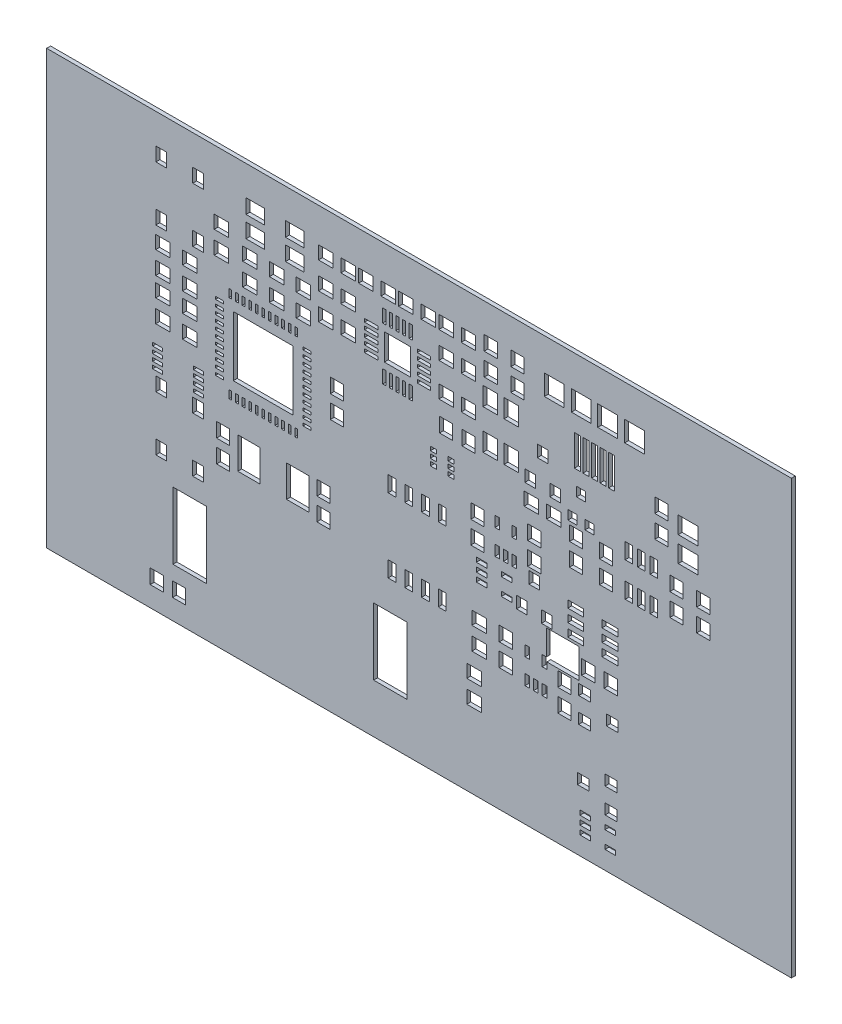
SolidWorks part; units mm, degrees
ref_plane "Front Plane" through (0, 0, 0) normal (0, 0, 1) x (1, 0, 0)
ref_plane "Top Plane" through (0, 0, 0) normal (0, 1, 0) x (1, 0, 0)
ref_plane "Right Plane" through (0, 0, 0) normal (1, 0, 0) x (0, 0, -1)
sketch "Model" plane through (0, 0, 0) normal (0, 0, 1) x (1, 0, 0)
  line L0 (20.5761, 267.496) -> (23.1161, 267.496)
  line L1 (23.1161, 267.496) -> (23.1161, 272.576)
  line L2 (23.1161, 272.576) -> (20.5761, 272.576)
  line L3 (20.5761, 272.576) -> (20.5761, 267.496)
  line L4 (5.3361, 267.496) -> (7.8761, 267.496)
  line L5 (7.8761, 267.496) -> (7.8761, 272.576)
  line L6 (7.8761, 272.576) -> (5.3361, 272.576)
  line L7 (5.3361, 272.576) -> (5.3361, 267.496)
  line L8 (34.554, 274.019) -> (35.554, 274.019)
  line L9 (35.554, 274.019) -> (35.554, 275.119)
  line L10 (35.554, 275.119) -> (34.554, 275.119)
  line L11 (34.554, 275.119) -> (34.554, 274.019)
  line L12 (34.554, 272.319) -> (35.554, 272.319)
  line L13 (35.554, 272.319) -> (35.554, 273.4189)
  line L14 (35.554, 273.4189) -> (34.554, 273.4189)
  line L15 (34.554, 273.4189) -> (34.554, 272.319)
  line L16 (43.7019, 286.724) -> (45.2019, 286.724)
  line L17 (45.2019, 286.724) -> (45.2019, 288.0239)
  line L18 (45.2019, 288.0239) -> (43.7019, 288.0239)
  line L19 (43.7019, 288.0239) -> (43.7019, 286.724)
  line L20 (43.7019, 288.624) -> (45.2019, 288.624)
  line L21 (45.2019, 288.624) -> (45.2019, 289.924)
  line L22 (45.2019, 289.924) -> (43.7019, 289.924)
  line L23 (43.7019, 289.924) -> (43.7019, 288.624)
  line L24 (24.1781, 293.0311) -> (25.2781, 293.0311)
  line L25 (25.2781, 293.0311) -> (25.2781, 294.031)
  line L26 (25.2781, 294.031) -> (24.1781, 294.031)
  line L27 (24.1781, 294.031) -> (24.1781, 293.0311)
  line L28 (22.4781, 293.0311) -> (23.5782, 293.0311)
  line L29 (23.5782, 293.0311) -> (23.5782, 294.031)
  line L30 (23.5782, 294.031) -> (22.4781, 294.031)
  line L31 (22.4781, 294.031) -> (22.4781, 293.0311)
  line L32 (41.92, 287.4319) -> (42.92, 287.4319)
  line L33 (42.92, 287.4319) -> (42.92, 288.532)
  line L34 (42.92, 288.532) -> (41.92, 288.532)
  line L35 (41.92, 288.532) -> (41.92, 287.4319)
  line L36 (41.92, 289.132) -> (42.92, 289.132)
  line L37 (42.92, 289.132) -> (42.92, 290.232)
  line L38 (42.92, 290.232) -> (41.92, 290.232)
  line L39 (41.92, 290.232) -> (41.92, 289.132)
  line L40 (30.109, 274.781) -> (31.109, 274.781)
  line L41 (31.109, 274.781) -> (31.109, 275.8809)
  line L42 (31.109, 275.8809) -> (30.109, 275.8809)
  line L43 (30.109, 275.8809) -> (30.109, 274.781)
  line L44 (30.109, 273.0811) -> (31.109, 273.0811)
  line L45 (31.109, 273.0811) -> (31.109, 274.181)
  line L46 (31.109, 274.181) -> (30.109, 274.181)
  line L47 (30.109, 274.181) -> (30.109, 273.0811)
  line L48 (17.282, 282.9869) -> (18.2821, 282.9869)
  line L49 (18.2821, 282.9869) -> (18.2821, 284.087)
  line L50 (18.2821, 284.087) -> (17.282, 284.087)
  line L51 (17.282, 284.087) -> (17.282, 282.9869)
  line L52 (17.282, 284.687) -> (18.2821, 284.687)
  line L53 (18.2821, 284.687) -> (18.2821, 285.787)
  line L54 (18.2821, 285.787) -> (17.282, 285.787)
  line L55 (17.282, 285.787) -> (17.282, 284.687)
  line L56 (16.2661, 275.748) -> (17.266, 275.748)
  line L57 (17.266, 275.748) -> (17.266, 276.8481)
  line L58 (17.266, 276.8481) -> (16.2661, 276.8481)
  line L59 (16.2661, 276.8481) -> (16.2661, 275.748)
  line L60 (16.2661, 277.4481) -> (17.266, 277.4481)
  line L61 (17.266, 277.4481) -> (17.266, 278.548)
  line L62 (17.266, 278.548) -> (16.2661, 278.548)
  line L63 (16.2661, 278.548) -> (16.2661, 277.4481)
  line L64 (43.063, 282.86) -> (44.063, 282.86)
  line L65 (44.063, 282.86) -> (44.063, 283.96)
  line L66 (44.063, 283.96) -> (43.063, 283.96)
  line L67 (43.063, 283.96) -> (43.063, 282.86)
  line L68 (43.063, 284.56) -> (44.063, 284.56)
  line L69 (44.063, 284.56) -> (44.063, 285.6601)
  line L70 (44.063, 285.6601) -> (43.063, 285.6601)
  line L71 (43.063, 285.6601) -> (43.063, 284.56)
  line L72 (45.095, 282.86) -> (46.095, 282.86)
  line L73 (46.095, 282.86) -> (46.095, 283.96)
  line L74 (46.095, 283.96) -> (45.095, 283.96)
  line L75 (45.095, 283.96) -> (45.095, 282.86)
  line L76 (45.095, 284.56) -> (46.095, 284.56)
  line L77 (46.095, 284.56) -> (46.095, 285.6601)
  line L78 (46.095, 285.6601) -> (45.095, 285.6601)
  line L79 (45.095, 285.6601) -> (45.095, 284.56)
  line L80 (8.6461, 277.4481) -> (9.646, 277.4481)
  line L81 (9.646, 277.4481) -> (9.646, 278.548)
  line L82 (9.646, 278.548) -> (8.6461, 278.548)
  line L83 (8.6461, 278.548) -> (8.6461, 277.4481)
  line L84 (8.6461, 275.748) -> (9.646, 275.748)
  line L85 (9.646, 275.748) -> (9.646, 276.8481)
  line L86 (9.646, 276.8481) -> (8.6461, 276.8481)
  line L87 (8.6461, 276.8481) -> (8.6461, 275.748)
  line L88 (18.0821, 290.999) -> (19.1821, 290.999)
  line L89 (19.1821, 290.999) -> (19.1821, 291.999)
  line L90 (19.1821, 291.999) -> (18.0821, 291.999)
  line L91 (18.0821, 291.999) -> (18.0821, 290.999)
  line L92 (16.382, 290.999) -> (17.4821, 290.999)
  line L93 (17.4821, 290.999) -> (17.4821, 291.999)
  line L94 (17.4821, 291.999) -> (16.382, 291.999)
  line L95 (16.382, 291.999) -> (16.382, 290.999)
  line L96 (37.729, 282.352) -> (38.729, 282.352)
  line L97 (38.729, 282.352) -> (38.729, 283.452)
  line L98 (38.729, 283.452) -> (37.729, 283.452)
  line L99 (37.729, 283.452) -> (37.729, 282.352)
  line L100 (37.729, 284.052) -> (38.729, 284.052)
  line L101 (38.729, 284.052) -> (38.729, 285.152)
  line L102 (38.729, 285.152) -> (37.729, 285.152)
  line L103 (37.729, 285.152) -> (37.729, 284.052)
  line L104 (28.966, 293.3231) -> (29.9659, 293.3231)
  line L105 (29.9659, 293.3231) -> (29.9659, 294.423)
  line L106 (29.9659, 294.423) -> (28.966, 294.423)
  line L107 (28.966, 294.423) -> (28.966, 293.3231)
  line L108 (28.966, 291.623) -> (29.9659, 291.623)
  line L109 (29.9659, 291.623) -> (29.9659, 292.7231)
  line L110 (29.9659, 292.7231) -> (28.966, 292.7231)
  line L111 (28.966, 292.7231) -> (28.966, 291.623)
  line L112 (30.998, 293.3231) -> (31.998, 293.3231)
  line L113 (31.998, 293.3231) -> (31.998, 294.423)
  line L114 (31.998, 294.423) -> (30.998, 294.423)
  line L115 (30.998, 294.423) -> (30.998, 293.3231)
  line L116 (30.998, 291.623) -> (31.998, 291.623)
  line L117 (31.998, 291.623) -> (31.998, 292.7231)
  line L118 (31.998, 292.7231) -> (30.998, 292.7231)
  line L119 (30.998, 292.7231) -> (30.998, 291.623)
  line L120 (25.5261, 293.0311) -> (26.6261, 293.0311)
  line L121 (26.6261, 293.0311) -> (26.6261, 294.031)
  line L122 (26.6261, 294.031) -> (25.5261, 294.031)
  line L123 (25.5261, 294.031) -> (25.5261, 293.0311)
  line L124 (27.2261, 293.0311) -> (28.3261, 293.0311)
  line L125 (28.3261, 293.0311) -> (28.3261, 294.031)
  line L126 (28.3261, 294.031) -> (27.2261, 294.031)
  line L127 (27.2261, 294.031) -> (27.2261, 293.0311)
  line L128 (25.5261, 290.999) -> (26.6261, 290.999)
  line L129 (26.6261, 290.999) -> (26.6261, 291.999)
  line L130 (26.6261, 291.999) -> (25.5261, 291.999)
  line L131 (25.5261, 291.999) -> (25.5261, 290.999)
  line L132 (27.2261, 290.999) -> (28.3261, 290.999)
  line L133 (28.3261, 290.999) -> (28.3261, 291.999)
  line L134 (28.3261, 291.999) -> (27.2261, 291.999)
  line L135 (27.2261, 291.999) -> (27.2261, 290.999)
  line L136 (33.6826, 277.5036) -> (33.6826, 275.577)
  line L137 (33.3701, 275.577) -> (33.6826, 275.577)
  line L138 (36.1719, 275.2684) -> (33.7201, 275.2684)
  line L139 (33.7201, 275.2684) -> (33.7201, 274.777)
  line L140 (9.5937, 280.5076) -> (9.7944, 280.5076)
  line L141 (9.7944, 280.5076) -> (9.7944, 281.1084)
  line L142 (9.7944, 281.1084) -> (9.5937, 281.1084)
  line L143 (9.5937, 281.1084) -> (9.5937, 280.5076)
  line L148 (10.0936, 280.5076) -> (10.2945, 280.5076)
  line L149 (10.2945, 280.5076) -> (10.2945, 281.1084)
  line L150 (10.2945, 281.1084) -> (10.0936, 281.1084)
  line L151 (10.0936, 281.1084) -> (10.0936, 280.5076)
  line L156 (10.5937, 280.5076) -> (10.7945, 280.5076)
  line L157 (10.7945, 280.5076) -> (10.7945, 281.1084)
  line L158 (10.7945, 281.1084) -> (10.5937, 281.1084)
  line L159 (10.5937, 281.1084) -> (10.5937, 280.5076)
  line L164 (11.0937, 280.5076) -> (11.2945, 280.5076)
  line L165 (11.2945, 280.5076) -> (11.2945, 281.1084)
  line L166 (11.2945, 281.1084) -> (11.0937, 281.1084)
  line L167 (11.0937, 281.1084) -> (11.0937, 280.5076)
  line L172 (11.5936, 280.5076) -> (11.7946, 280.5076)
  line L173 (11.7946, 280.5076) -> (11.7946, 281.1084)
  line L174 (11.7946, 281.1084) -> (11.5936, 281.1084)
  line L175 (11.5936, 281.1084) -> (11.5936, 280.5076)
  line L180 (12.0937, 280.5076) -> (12.2945, 280.5076)
  line L181 (12.2945, 280.5076) -> (12.2945, 281.1084)
  line L182 (12.2945, 281.1084) -> (12.0937, 281.1084)
  line L183 (12.0937, 281.1084) -> (12.0937, 280.5076)
  line L188 (12.5937, 280.5076) -> (12.7944, 280.5076)
  line L189 (12.7944, 280.5076) -> (12.7944, 281.1084)
  line L190 (12.7944, 281.1084) -> (12.5937, 281.1084)
  line L191 (12.5937, 281.1084) -> (12.5937, 280.5076)
  line L196 (13.0938, 280.5076) -> (13.2945, 280.5076)
  line L197 (13.2945, 280.5076) -> (13.2945, 281.1084)
  line L198 (13.2945, 281.1084) -> (13.0938, 281.1084)
  line L199 (13.0938, 281.1084) -> (13.0938, 280.5076)
  line L204 (13.5937, 280.5076) -> (13.7945, 280.5076)
  line L205 (13.7945, 280.5076) -> (13.7945, 281.1084)
  line L206 (13.7945, 281.1084) -> (13.5937, 281.1084)
  line L207 (13.5937, 281.1084) -> (13.5937, 280.5076)
  line L212 (14.0937, 280.5076) -> (14.2944, 280.5076)
  line L213 (14.2944, 280.5076) -> (14.2944, 281.1084)
  line L214 (14.2944, 281.1084) -> (14.0937, 281.1084)
  line L215 (14.0937, 281.1084) -> (14.0937, 280.5076)
  line L220 (14.5938, 280.5076) -> (14.7945, 280.5076)
  line L221 (14.7945, 280.5076) -> (14.7945, 281.1084)
  line L222 (14.7945, 281.1084) -> (14.5938, 281.1084)
  line L223 (14.5938, 281.1084) -> (14.5938, 280.5076)
  line L228 (15.2187, 281.5326) -> (15.8195, 281.5326)
  line L229 (15.8195, 281.5326) -> (15.8195, 281.7333)
  line L230 (15.8195, 281.7333) -> (15.2187, 281.7333)
  line L231 (15.2187, 281.7333) -> (15.2187, 281.5326)
  line L236 (15.2187, 282.0327) -> (15.8195, 282.0327)
  line L237 (15.8195, 282.0327) -> (15.8195, 282.2334)
  line L238 (15.8195, 282.2334) -> (15.2187, 282.2334)
  line L239 (15.2187, 282.2334) -> (15.2187, 282.0327)
  line L244 (15.2187, 282.5326) -> (15.8195, 282.5326)
  line L245 (15.8195, 282.5326) -> (15.8195, 282.7334)
  line L246 (15.8195, 282.7334) -> (15.2187, 282.7334)
  line L247 (15.2187, 282.7334) -> (15.2187, 282.5326)
  line L252 (15.2187, 283.0326) -> (15.8195, 283.0326)
  line L253 (15.8195, 283.0326) -> (15.8195, 283.2333)
  line L254 (15.8195, 283.2333) -> (15.2187, 283.2333)
  line L255 (15.2187, 283.2333) -> (15.2187, 283.0326)
  line L260 (15.2187, 283.5327) -> (15.8195, 283.5327)
  line L261 (15.8195, 283.5327) -> (15.8195, 283.7334)
  line L262 (15.8195, 283.7334) -> (15.2187, 283.7334)
  line L263 (15.2187, 283.7334) -> (15.2187, 283.5327)
  line L268 (15.2187, 284.0326) -> (15.8195, 284.0326)
  line L269 (15.8195, 284.0326) -> (15.8195, 284.2334)
  line L270 (15.8195, 284.2334) -> (15.2187, 284.2334)
  line L271 (15.2187, 284.2334) -> (15.2187, 284.0326)
  line L276 (15.2187, 284.5325) -> (15.8195, 284.5325)
  line L277 (15.8195, 284.5325) -> (15.8195, 284.7335)
  line L278 (15.8195, 284.7335) -> (15.2187, 284.7335)
  line L279 (15.2187, 284.7335) -> (15.2187, 284.5325)
  line L284 (15.2187, 285.0326) -> (15.8195, 285.0326)
  line L285 (15.8195, 285.0326) -> (15.8195, 285.2334)
  line L286 (15.8195, 285.2334) -> (15.2187, 285.2334)
  line L287 (15.2187, 285.2334) -> (15.2187, 285.0326)
  line L292 (15.2187, 285.5326) -> (15.8195, 285.5326)
  line L293 (15.8195, 285.5326) -> (15.8195, 285.7334)
  line L294 (15.8195, 285.7334) -> (15.2187, 285.7334)
  line L295 (15.2187, 285.7334) -> (15.2187, 285.5326)
  line L300 (15.2187, 286.0326) -> (15.8195, 286.0326)
  line L301 (15.8195, 286.0326) -> (15.8195, 286.2335)
  line L302 (15.8195, 286.2335) -> (15.2187, 286.2335)
  line L303 (15.2187, 286.2335) -> (15.2187, 286.0326)
  line L308 (15.2187, 286.5326) -> (15.8195, 286.5326)
  line L309 (15.8195, 286.5326) -> (15.8195, 286.7334)
  line L310 (15.8195, 286.7334) -> (15.2187, 286.7334)
  line L311 (15.2187, 286.7334) -> (15.2187, 286.5326)
  line L316 (14.5938, 287.1576) -> (14.7945, 287.1576)
  line L317 (14.7945, 287.1576) -> (14.7945, 287.7584)
  line L318 (14.7945, 287.7584) -> (14.5938, 287.7584)
  line L319 (14.5938, 287.7584) -> (14.5938, 287.1576)
  line L324 (14.0937, 287.1576) -> (14.2944, 287.1576)
  line L325 (14.2944, 287.1576) -> (14.2944, 287.7584)
  line L326 (14.2944, 287.7584) -> (14.0937, 287.7584)
  line L327 (14.0937, 287.7584) -> (14.0937, 287.1576)
  line L332 (13.5937, 287.1576) -> (13.7945, 287.1576)
  line L333 (13.7945, 287.1576) -> (13.7945, 287.7584)
  line L334 (13.7945, 287.7584) -> (13.5937, 287.7584)
  line L335 (13.5937, 287.7584) -> (13.5937, 287.1576)
  line L340 (13.0938, 287.1576) -> (13.2945, 287.1576)
  line L341 (13.2945, 287.1576) -> (13.2945, 287.7584)
  line L342 (13.2945, 287.7584) -> (13.0938, 287.7584)
  line L343 (13.0938, 287.7584) -> (13.0938, 287.1576)
  line L348 (12.5937, 287.1576) -> (12.7944, 287.1576)
  line L349 (12.7944, 287.1576) -> (12.7944, 287.7584)
  line L350 (12.7944, 287.7584) -> (12.5937, 287.7584)
  line L351 (12.5937, 287.7584) -> (12.5937, 287.1576)
  line L356 (12.0937, 287.1576) -> (12.2945, 287.1576)
  line L357 (12.2945, 287.1576) -> (12.2945, 287.7584)
  line L358 (12.2945, 287.7584) -> (12.0937, 287.7584)
  line L359 (12.0937, 287.7584) -> (12.0937, 287.1576)
  line L364 (11.5936, 287.1576) -> (11.7946, 287.1576)
  line L365 (11.7946, 287.1576) -> (11.7946, 287.7584)
  line L366 (11.7946, 287.7584) -> (11.5936, 287.7584)
  line L367 (11.5936, 287.7584) -> (11.5936, 287.1576)
  line L372 (11.0937, 287.1576) -> (11.2945, 287.1576)
  line L373 (11.2945, 287.1576) -> (11.2945, 287.7584)
  line L374 (11.2945, 287.7584) -> (11.0937, 287.7584)
  line L375 (11.0937, 287.7584) -> (11.0937, 287.1576)
  line L380 (10.5937, 287.1576) -> (10.7945, 287.1576)
  line L381 (10.7945, 287.1576) -> (10.7945, 287.7584)
  line L382 (10.7945, 287.7584) -> (10.5937, 287.7584)
  line L383 (10.5937, 287.7584) -> (10.5937, 287.1576)
  line L388 (10.0936, 287.1576) -> (10.2945, 287.1576)
  line L389 (10.2945, 287.1576) -> (10.2945, 287.7584)
  line L390 (10.2945, 287.7584) -> (10.0936, 287.7584)
  line L391 (10.0936, 287.7584) -> (10.0936, 287.1576)
  line L396 (9.5937, 287.1576) -> (9.7944, 287.1576)
  line L397 (9.7944, 287.1576) -> (9.7944, 287.7584)
  line L398 (9.7944, 287.7584) -> (9.5937, 287.7584)
  line L399 (9.5937, 287.7584) -> (9.5937, 287.1576)
  line L404 (8.5687, 286.5326) -> (9.1695, 286.5326)
  line L405 (9.1695, 286.5326) -> (9.1695, 286.7334)
  line L406 (9.1695, 286.7334) -> (8.5687, 286.7334)
  line L407 (8.5687, 286.7334) -> (8.5687, 286.5326)
  line L412 (8.5687, 286.0326) -> (9.1695, 286.0326)
  line L413 (9.1695, 286.0326) -> (9.1695, 286.2335)
  line L414 (9.1695, 286.2335) -> (8.5687, 286.2335)
  line L415 (8.5687, 286.2335) -> (8.5687, 286.0326)
  line L420 (8.5687, 285.5326) -> (9.1695, 285.5326)
  line L421 (9.1695, 285.5326) -> (9.1695, 285.7334)
  line L422 (9.1695, 285.7334) -> (8.5687, 285.7334)
  line L423 (8.5687, 285.7334) -> (8.5687, 285.5326)
  line L428 (8.5687, 285.0326) -> (9.1695, 285.0326)
  line L429 (9.1695, 285.0326) -> (9.1695, 285.2334)
  line L430 (9.1695, 285.2334) -> (8.5687, 285.2334)
  line L431 (8.5687, 285.2334) -> (8.5687, 285.0326)
  line L436 (8.5687, 284.5325) -> (9.1695, 284.5325)
  line L437 (9.1695, 284.5325) -> (9.1695, 284.7335)
  line L438 (9.1695, 284.7335) -> (8.5687, 284.7335)
  line L439 (8.5687, 284.7335) -> (8.5687, 284.5325)
  line L444 (8.5687, 284.0326) -> (9.1695, 284.0326)
  line L445 (9.1695, 284.0326) -> (9.1695, 284.2334)
  line L446 (9.1695, 284.2334) -> (8.5687, 284.2334)
  line L447 (8.5687, 284.2334) -> (8.5687, 284.0326)
  line L452 (8.5687, 283.5327) -> (9.1695, 283.5327)
  line L453 (9.1695, 283.5327) -> (9.1695, 283.7334)
  line L454 (9.1695, 283.7334) -> (8.5687, 283.7334)
  line L455 (8.5687, 283.7334) -> (8.5687, 283.5327)
  line L460 (8.5687, 283.0326) -> (9.1695, 283.0326)
  line L461 (9.1695, 283.0326) -> (9.1695, 283.2333)
  line L462 (9.1695, 283.2333) -> (8.5687, 283.2333)
  line L463 (8.5687, 283.2333) -> (8.5687, 283.0326)
  line L468 (8.5687, 282.5326) -> (9.1695, 282.5326)
  line L469 (9.1695, 282.5326) -> (9.1695, 282.7334)
  line L470 (9.1695, 282.7334) -> (8.5687, 282.7334)
  line L471 (8.5687, 282.7334) -> (8.5687, 282.5326)
  line L476 (8.5687, 282.0327) -> (9.1695, 282.0327)
  line L477 (9.1695, 282.0327) -> (9.1695, 282.2334)
  line L478 (9.1695, 282.2334) -> (8.5687, 282.2334)
  line L479 (8.5687, 282.2334) -> (8.5687, 282.0327)
  line L484 (8.5687, 281.5326) -> (9.1695, 281.5326)
  line L485 (9.1695, 281.5326) -> (9.1695, 281.7333)
  line L486 (9.1695, 281.7333) -> (8.5687, 281.7333)
  line L487 (8.5687, 281.7333) -> (8.5687, 281.5326)
  line L492 (9.9188, 281.8576) -> (14.4694, 281.8576)
  line L493 (14.4694, 281.8576) -> (14.4694, 286.4083)
  line L494 (14.4694, 286.4083) -> (9.9188, 286.4083)
  line L495 (9.9188, 286.4083) -> (9.9188, 281.8576)
  line L497 (36.1719, 275.2684) -> (36.1719, 277.5036)
  line L498 (36.1719, 277.5036) -> (33.6826, 277.5036)
  line L500 (38.4152, 289.054) -> (38.8652, 289.054)
  line L501 (38.8652, 289.054) -> (38.8652, 291.404)
  line L502 (38.8652, 291.404) -> (38.4152, 291.404)
  line L503 (38.4152, 291.404) -> (38.4152, 289.054)
  line L504 (37.765, 289.054) -> (38.2151, 289.054)
  line L505 (38.2151, 289.054) -> (38.2151, 291.404)
  line L506 (38.2151, 291.404) -> (37.765, 291.404)
  line L507 (37.765, 291.404) -> (37.765, 289.054)
  line L508 (37.1152, 289.054) -> (37.5652, 289.054)
  line L509 (37.5652, 289.054) -> (37.5652, 291.404)
  line L510 (37.5652, 291.404) -> (37.1152, 291.404)
  line L511 (37.1152, 291.404) -> (37.1152, 289.054)
  line L512 (36.465, 289.054) -> (36.9149, 289.054)
  line L513 (36.9149, 289.054) -> (36.9149, 291.404)
  line L514 (36.9149, 291.404) -> (36.465, 291.404)
  line L515 (36.465, 291.404) -> (36.465, 289.054)
  line L516 (35.8152, 289.054) -> (36.2651, 289.054)
  line L517 (36.2651, 289.054) -> (36.2651, 291.404)
  line L518 (36.2651, 291.404) -> (35.8152, 291.404)
  line L519 (35.8152, 291.404) -> (35.8152, 289.054)
  line L520 (37.59, 292.6289) -> (39.09, 292.6289)
  line L521 (39.09, 292.6289) -> (39.09, 294.1789)
  line L522 (39.09, 294.1789) -> (37.59, 294.1789)
  line L523 (37.59, 294.1789) -> (37.59, 292.6289)
  line L524 (35.5901, 292.6289) -> (37.0901, 292.6289)
  line L525 (37.0901, 292.6289) -> (37.0901, 294.1789)
  line L526 (37.0901, 294.1789) -> (35.5901, 294.1789)
  line L527 (35.5901, 294.1789) -> (35.5901, 292.6289)
  line L528 (39.64, 292.6289) -> (41.14, 292.6289)
  line L529 (41.14, 292.6289) -> (41.14, 294.1789)
  line L530 (41.14, 294.1789) -> (39.64, 294.1789)
  line L531 (39.64, 294.1789) -> (39.64, 292.6289)
  line L532 (33.5401, 292.6289) -> (35.0401, 292.6289)
  line L533 (35.0401, 292.6289) -> (35.0401, 294.1789)
  line L534 (35.0401, 294.1789) -> (33.5401, 294.1789)
  line L535 (33.5401, 294.1789) -> (33.5401, 292.6289)
  line L536 (38.1442, 267.4159) -> (39.0442, 267.4159)
  line L537 (39.0442, 267.4159) -> (39.0442, 268.216)
  line L538 (39.0442, 268.216) -> (38.1442, 268.216)
  line L539 (38.1442, 268.216) -> (38.1442, 267.4159)
  line L540 (38.1442, 269.316) -> (39.0442, 269.316)
  line L541 (39.0442, 269.316) -> (39.0442, 270.1161)
  line L542 (39.0442, 270.1161) -> (38.1442, 270.1161)
  line L543 (38.1442, 270.1161) -> (38.1442, 269.316)
  line L544 (36.0441, 268.366) -> (36.9441, 268.366)
  line L545 (36.9441, 268.366) -> (36.9441, 269.1661)
  line L546 (36.9441, 269.1661) -> (36.0441, 269.1661)
  line L547 (36.0441, 269.1661) -> (36.0441, 268.366)
  line L548 (36.144, 274.2691) -> (37.044, 274.2691)
  line L549 (37.044, 274.2691) -> (37.044, 275.069)
  line L550 (37.044, 275.069) -> (36.144, 275.069)
  line L551 (36.144, 275.069) -> (36.144, 274.2691)
  line L552 (36.144, 272.369) -> (37.044, 272.369)
  line L553 (37.044, 272.369) -> (37.044, 273.169)
  line L554 (37.044, 273.169) -> (36.144, 273.169)
  line L555 (36.144, 273.169) -> (36.144, 272.369)
  line L556 (38.2441, 273.319) -> (39.1441, 273.319)
  line L557 (39.1441, 273.319) -> (39.1441, 274.119)
  line L558 (39.1441, 274.119) -> (38.2441, 274.119)
  line L559 (38.2441, 274.119) -> (38.2441, 273.319)
  line L560 (28.0273, 273.1309) -> (29.1272, 273.1309)
  line L561 (29.1272, 273.1309) -> (29.1272, 274.131)
  line L562 (29.1272, 274.131) -> (28.0273, 274.131)
  line L563 (28.0273, 274.131) -> (28.0273, 273.1309)
  line L564 (28.0273, 274.831) -> (29.1272, 274.831)
  line L565 (29.1272, 274.831) -> (29.1272, 275.8311)
  line L566 (29.1272, 275.8311) -> (28.0273, 275.8311)
  line L567 (28.0273, 275.8311) -> (28.0273, 274.831)
  line L568 (16.382, 293.0311) -> (17.4821, 293.0311)
  line L569 (17.4821, 293.0311) -> (17.4821, 294.031)
  line L570 (17.4821, 294.031) -> (16.382, 294.031)
  line L571 (16.382, 294.031) -> (16.382, 293.0311)
  line L572 (18.0821, 293.0311) -> (19.1821, 293.0311)
  line L573 (19.1821, 293.0311) -> (19.1821, 294.031)
  line L574 (19.1821, 294.031) -> (18.0821, 294.031)
  line L575 (18.0821, 294.031) -> (18.0821, 293.0311)
  line L576 (6.0561, 282.6559) -> (7.1561, 282.6559)
  line L577 (7.1561, 282.6559) -> (7.1561, 283.656)
  line L578 (7.1561, 283.656) -> (6.0561, 283.656)
  line L579 (6.0561, 283.656) -> (6.0561, 282.6559)
  line L580 (6.0561, 284.356) -> (7.1561, 284.356)
  line L581 (7.1561, 284.356) -> (7.1561, 285.3561)
  line L582 (7.1561, 285.3561) -> (6.0561, 285.3561)
  line L583 (6.0561, 285.3561) -> (6.0561, 284.356)
  line L584 (36.3712, 275.709) -> (37.3712, 275.709)
  line L585 (37.3712, 275.709) -> (37.3712, 276.8091)
  line L586 (37.3712, 276.8091) -> (36.3712, 276.8091)
  line L587 (36.3712, 276.8091) -> (36.3712, 275.709)
  line L588 (38.0712, 275.709) -> (39.0712, 275.709)
  line L589 (39.0712, 275.709) -> (39.0712, 276.8091)
  line L590 (39.0712, 276.8091) -> (38.0712, 276.8091)
  line L591 (38.0712, 276.8091) -> (38.0712, 275.709)
  line L592 (8.469, 289.387) -> (9.5691, 289.387)
  line L593 (9.5691, 289.387) -> (9.5691, 290.387)
  line L594 (9.5691, 290.387) -> (8.469, 290.387)
  line L595 (8.469, 290.387) -> (8.469, 289.387)
  line L596 (8.469, 291.087) -> (9.5691, 291.087)
  line L597 (9.5691, 291.087) -> (9.5691, 292.087)
  line L598 (9.5691, 292.087) -> (8.469, 292.087)
  line L599 (8.469, 292.087) -> (8.469, 291.087)
  line L600 (12.6601, 288.3709) -> (13.76, 288.3709)
  line L601 (13.76, 288.3709) -> (13.76, 289.371)
  line L602 (13.76, 289.371) -> (12.6601, 289.371)
  line L603 (12.6601, 289.371) -> (12.6601, 288.3709)
  line L604 (12.6601, 290.071) -> (13.76, 290.071)
  line L605 (13.76, 290.071) -> (13.76, 291.0711)
  line L606 (13.76, 291.0711) -> (12.6601, 291.0711)
  line L607 (12.6601, 291.0711) -> (12.6601, 290.071)
  line L608 (5.3051, 265.295) -> (6.3051, 265.295)
  line L609 (6.3051, 265.295) -> (6.3051, 266.395)
  line L610 (6.3051, 266.395) -> (5.3051, 266.395)
  line L611 (5.3051, 266.395) -> (5.3051, 265.295)
  line L612 (3.6051, 265.295) -> (4.605, 265.295)
  line L613 (4.605, 265.295) -> (4.605, 266.395)
  line L614 (4.605, 266.395) -> (3.6051, 266.395)
  line L615 (3.6051, 266.395) -> (3.6051, 265.295)
  line L616 (25.576, 286.25) -> (26.5761, 286.25)
  line L617 (26.5761, 286.25) -> (26.5761, 287.35)
  line L618 (26.5761, 287.35) -> (25.576, 287.35)
  line L619 (25.576, 287.35) -> (25.576, 286.25)
  line L620 (27.2762, 286.25) -> (28.2762, 286.25)
  line L621 (28.2762, 286.25) -> (28.2762, 287.35)
  line L622 (28.2762, 287.35) -> (27.2762, 287.35)
  line L623 (27.2762, 287.35) -> (27.2762, 286.25)
  line L624 (10.628, 288.3709) -> (11.7281, 288.3709)
  line L625 (11.7281, 288.3709) -> (11.7281, 289.371)
  line L626 (11.7281, 289.371) -> (10.628, 289.371)
  line L627 (10.628, 289.371) -> (10.628, 288.3709)
  line L628 (10.628, 290.071) -> (11.7281, 290.071)
  line L629 (11.7281, 290.071) -> (11.7281, 291.0711)
  line L630 (11.7281, 291.0711) -> (10.628, 291.0711)
  line L631 (10.628, 291.0711) -> (10.628, 290.071)
  line L632 (14.6922, 288.3709) -> (15.7921, 288.3709)
  line L633 (15.7921, 288.3709) -> (15.7921, 289.371)
  line L634 (15.7921, 289.371) -> (14.6922, 289.371)
  line L635 (14.6922, 289.371) -> (14.6922, 288.3709)
  line L636 (14.6922, 290.071) -> (15.7921, 290.071)
  line L637 (15.7921, 290.071) -> (15.7921, 291.0711)
  line L638 (15.7921, 291.0711) -> (14.6922, 291.0711)
  line L639 (14.6922, 291.0711) -> (14.6922, 290.071)
  line L640 (27.6463, 269.448) -> (28.7462, 269.448)
  line L641 (28.7462, 269.448) -> (28.7462, 270.4481)
  line L642 (28.7462, 270.4481) -> (27.6463, 270.4481)
  line L643 (27.6463, 270.4481) -> (27.6463, 269.448)
  line L644 (27.6463, 271.1479) -> (28.7462, 271.1479)
  line L645 (28.7462, 271.1479) -> (28.7462, 272.148)
  line L646 (28.7462, 272.148) -> (27.6463, 272.148)
  line L647 (27.6463, 272.148) -> (27.6463, 271.1479)
  line L648 (27.2261, 288.459) -> (28.3261, 288.459)
  line L649 (28.3261, 288.459) -> (28.3261, 289.459)
  line L650 (28.3261, 289.459) -> (27.2261, 289.459)
  line L651 (27.2261, 289.459) -> (27.2261, 288.459)
  line L652 (25.5261, 288.459) -> (26.6261, 288.459)
  line L653 (26.6261, 288.459) -> (26.6261, 289.459)
  line L654 (26.6261, 289.459) -> (25.5261, 289.459)
  line L655 (25.5261, 289.459) -> (25.5261, 288.459)
  line L656 (19.4301, 293.0311) -> (20.5301, 293.0311)
  line L657 (20.5301, 293.0311) -> (20.5301, 294.031)
  line L658 (20.5301, 294.031) -> (19.4301, 294.031)
  line L659 (19.4301, 294.031) -> (19.4301, 293.0311)
  line L660 (21.1301, 293.0311) -> (22.2302, 293.0311)
  line L661 (22.2302, 293.0311) -> (22.2302, 294.031)
  line L662 (22.2302, 294.031) -> (21.1301, 294.031)
  line L663 (21.1301, 294.031) -> (21.1301, 293.0311)
  line L664 (4.024, 285.8309) -> (5.1241, 285.8309)
  line L665 (5.1241, 285.8309) -> (5.1241, 286.831)
  line L666 (5.1241, 286.831) -> (4.024, 286.831)
  line L667 (4.024, 286.831) -> (4.024, 285.8309)
  line L668 (4.024, 287.531) -> (5.1241, 287.531)
  line L669 (5.1241, 287.531) -> (5.1241, 288.5311)
  line L670 (5.1241, 288.5311) -> (4.024, 288.5311)
  line L671 (4.024, 288.5311) -> (4.024, 287.531)
  line L672 (16.382, 288.967) -> (17.4821, 288.967)
  line L673 (17.4821, 288.967) -> (17.4821, 289.967)
  line L674 (17.4821, 289.967) -> (16.382, 289.967)
  line L675 (16.382, 289.967) -> (16.382, 288.967)
  line L676 (18.0821, 288.967) -> (19.1821, 288.967)
  line L677 (19.1821, 288.967) -> (19.1821, 289.967)
  line L678 (19.1821, 289.967) -> (18.0821, 289.967)
  line L679 (18.0821, 289.967) -> (18.0821, 288.967)
  line L680 (4.024, 282.6559) -> (5.1241, 282.6559)
  line L681 (5.1241, 282.6559) -> (5.1241, 283.656)
  line L682 (5.1241, 283.656) -> (4.024, 283.656)
  line L683 (4.024, 283.656) -> (4.024, 282.6559)
  line L684 (4.024, 284.356) -> (5.1241, 284.356)
  line L685 (5.1241, 284.356) -> (5.1241, 285.3561)
  line L686 (5.1241, 285.3561) -> (4.024, 285.3561)
  line L687 (4.024, 285.3561) -> (4.024, 284.356)
  line L688 (6.0561, 285.8309) -> (7.1561, 285.8309)
  line L689 (7.1561, 285.8309) -> (7.1561, 286.831)
  line L690 (7.1561, 286.831) -> (6.0561, 286.831)
  line L691 (6.0561, 286.831) -> (6.0561, 285.8309)
  line L692 (6.0561, 287.531) -> (7.1561, 287.531)
  line L693 (7.1561, 287.531) -> (7.1561, 288.5311)
  line L694 (7.1561, 288.5311) -> (6.0561, 288.5311)
  line L695 (6.0561, 288.5311) -> (6.0561, 287.531)
  line L696 (21.6731, 274.7641) -> (22.2731, 274.7641)
  line L697 (22.2731, 274.7641) -> (22.2731, 275.964)
  line L698 (22.2731, 275.964) -> (21.6731, 275.964)
  line L699 (21.6731, 275.964) -> (21.6731, 274.7641)
  line L700 (22.9431, 274.7641) -> (23.5431, 274.7641)
  line L701 (23.5431, 274.7641) -> (23.5431, 275.964)
  line L702 (23.5431, 275.964) -> (22.9431, 275.964)
  line L703 (22.9431, 275.964) -> (22.9431, 274.7641)
  line L704 (24.2131, 274.7641) -> (24.8131, 274.7641)
  line L705 (24.8131, 274.7641) -> (24.8131, 275.964)
  line L706 (24.8131, 275.964) -> (24.2131, 275.964)
  line L707 (24.2131, 275.964) -> (24.2131, 274.7641)
  line L708 (25.4831, 274.7641) -> (26.0831, 274.7641)
  line L709 (26.0831, 274.7641) -> (26.0831, 275.964)
  line L710 (26.0831, 275.964) -> (25.4831, 275.964)
  line L711 (25.4831, 275.964) -> (25.4831, 274.7641)
  line L712 (25.4831, 280.364) -> (26.0831, 280.364)
  line L713 (26.0831, 280.364) -> (26.0831, 281.564)
  line L714 (26.0831, 281.564) -> (25.4831, 281.564)
  line L715 (25.4831, 281.564) -> (25.4831, 280.364)
  line L716 (24.2131, 280.364) -> (24.8131, 280.364)
  line L717 (24.8131, 280.364) -> (24.8131, 281.564)
  line L718 (24.8131, 281.564) -> (24.2131, 281.564)
  line L719 (24.2131, 281.564) -> (24.2131, 280.364)
  line L720 (22.9431, 280.364) -> (23.5431, 280.364)
  line L721 (23.5431, 280.364) -> (23.5431, 281.564)
  line L722 (23.5431, 281.564) -> (22.9431, 281.564)
  line L723 (22.9431, 281.564) -> (22.9431, 280.364)
  line L724 (21.6731, 280.364) -> (22.2731, 280.364)
  line L725 (22.2731, 280.364) -> (22.2731, 281.564)
  line L726 (22.2731, 281.564) -> (21.6731, 281.564)
  line L727 (21.6731, 281.564) -> (21.6731, 280.364)
  line L728 (13.9561, 276.075) -> (15.6561, 276.075)
  line L729 (15.6561, 276.075) -> (15.6561, 278.475)
  line L730 (15.6561, 278.475) -> (13.9561, 278.475)
  line L731 (13.9561, 278.475) -> (13.9561, 276.075)
  line L732 (10.2561, 276.075) -> (11.9561, 276.075)
  line L733 (11.9561, 276.075) -> (11.9561, 278.475)
  line L734 (11.9561, 278.475) -> (10.2561, 278.475)
  line L735 (10.2561, 278.475) -> (10.2561, 276.075)
  line L736 (13.8831, 291.673) -> (15.283, 291.673)
  line L737 (15.283, 291.673) -> (15.283, 292.773)
  line L738 (15.283, 292.773) -> (13.8831, 292.773)
  line L739 (13.8831, 292.773) -> (13.8831, 291.673)
  line L740 (10.8831, 291.673) -> (12.2831, 291.673)
  line L741 (12.2831, 291.673) -> (12.2831, 292.773)
  line L742 (12.2831, 292.773) -> (10.8831, 292.773)
  line L743 (10.8831, 292.773) -> (10.8831, 291.673)
  line L744 (10.8831, 293.273) -> (12.2831, 293.273)
  line L745 (12.2831, 293.273) -> (12.2831, 294.373)
  line L746 (12.2831, 294.373) -> (10.8831, 294.373)
  line L747 (10.8831, 294.373) -> (10.8831, 293.273)
  line L748 (13.8831, 293.273) -> (15.283, 293.273)
  line L749 (15.283, 293.273) -> (15.283, 294.373)
  line L750 (15.283, 294.373) -> (13.8831, 294.373)
  line L751 (13.8831, 294.373) -> (13.8831, 293.273)
  line L752 (28.8782, 286.632) -> (29.9781, 286.632)
  line L753 (29.9781, 286.632) -> (29.9781, 288.0319)
  line L754 (29.9781, 288.0319) -> (28.8782, 288.0319)
  line L755 (28.8782, 288.0319) -> (28.8782, 286.632)
  line L756 (28.8782, 289.632) -> (29.9781, 289.632)
  line L757 (29.9781, 289.632) -> (29.9781, 291.0321)
  line L758 (29.9781, 291.0321) -> (28.8782, 291.0321)
  line L759 (28.8782, 291.0321) -> (28.8782, 289.632)
  line L760 (30.478, 289.632) -> (31.578, 289.632)
  line L761 (31.578, 289.632) -> (31.578, 291.0321)
  line L762 (31.578, 291.0321) -> (30.478, 291.0321)
  line L763 (30.478, 291.0321) -> (30.478, 289.632)
  line L764 (30.478, 286.632) -> (31.578, 286.632)
  line L765 (31.578, 286.632) -> (31.578, 288.0319)
  line L766 (31.578, 288.0319) -> (30.478, 288.0319)
  line L767 (30.478, 288.0319) -> (30.478, 286.632)
  line L768 (38.1442, 265.147) -> (38.9442, 265.147)
  line L769 (38.9442, 265.147) -> (38.9442, 265.497)
  line L770 (38.9442, 265.497) -> (38.1442, 265.497)
  line L771 (38.1442, 265.497) -> (38.1442, 265.147)
  line L772 (38.1442, 266.447) -> (38.9442, 266.447)
  line L773 (38.9442, 266.447) -> (38.9442, 266.7971)
  line L774 (38.9442, 266.7971) -> (38.1442, 266.7971)
  line L775 (38.1442, 266.7971) -> (38.1442, 266.447)
  line L776 (36.2442, 266.447) -> (37.0441, 266.447)
  line L777 (37.0441, 266.447) -> (37.0441, 266.7971)
  line L778 (37.0441, 266.7971) -> (36.2442, 266.7971)
  line L779 (36.2442, 266.7971) -> (36.2442, 266.447)
  line L780 (36.2442, 265.797) -> (37.0441, 265.797)
  line L781 (37.0441, 265.797) -> (37.0441, 266.147)
  line L782 (37.0441, 266.147) -> (36.2442, 266.147)
  line L783 (36.2442, 266.147) -> (36.2442, 265.797)
  line L784 (36.2442, 265.147) -> (37.0441, 265.147)
  line L785 (37.0441, 265.147) -> (37.0441, 265.497)
  line L786 (37.0441, 265.497) -> (36.2442, 265.497)
  line L787 (36.2442, 265.497) -> (36.2442, 265.147)
  line L788 (4.0378, 289.1531) -> (4.8503, 289.1531)
  line L789 (4.8503, 289.1531) -> (4.8503, 290.203)
  line L790 (4.8503, 290.203) -> (4.0378, 290.203)
  line L791 (4.0378, 290.203) -> (4.0378, 289.1531)
  line L792 (4.0378, 293.3031) -> (4.8503, 293.3031)
  line L793 (4.8503, 293.3031) -> (4.8503, 294.353)
  line L794 (4.8503, 294.353) -> (4.0378, 294.353)
  line L795 (4.0378, 294.353) -> (4.0378, 293.3031)
  line L796 (6.8379, 293.3031) -> (7.6504, 293.3031)
  line L797 (7.6504, 293.3031) -> (7.6504, 294.353)
  line L798 (7.6504, 294.353) -> (6.8379, 294.353)
  line L799 (6.8379, 294.353) -> (6.8379, 293.3031)
  line L800 (6.8379, 289.1531) -> (7.6504, 289.1531)
  line L801 (7.6504, 289.1531) -> (7.6504, 290.203)
  line L802 (7.6504, 290.203) -> (6.8379, 290.203)
  line L803 (6.8379, 290.203) -> (6.8379, 289.1531)
  line L804 (33.3701, 274.777) -> (33.7201, 274.777)
  line L807 (33.3701, 275.577) -> (33.3701, 274.777)
  line L808 (32.0701, 274.777) -> (32.4201, 274.777)
  line L809 (32.4201, 274.777) -> (32.4201, 275.577)
  line L810 (32.4201, 275.577) -> (32.0701, 275.577)
  line L811 (32.0701, 275.577) -> (32.0701, 274.777)
  line L812 (32.0701, 272.877) -> (32.4201, 272.877)
  line L813 (32.4201, 272.877) -> (32.4201, 273.6771)
  line L814 (32.4201, 273.6771) -> (32.0701, 273.6771)
  line L815 (32.0701, 273.6771) -> (32.0701, 272.877)
  line L816 (32.7199, 272.877) -> (33.0699, 272.877)
  line L817 (33.0699, 272.877) -> (33.0699, 273.6771)
  line L818 (33.0699, 273.6771) -> (32.7199, 273.6771)
  line L819 (32.7199, 273.6771) -> (32.7199, 272.877)
  line L820 (33.3701, 272.877) -> (33.7201, 272.877)
  line L821 (33.7201, 272.877) -> (33.7201, 273.6771)
  line L822 (33.7201, 273.6771) -> (33.3701, 273.6771)
  line L823 (33.3701, 273.6771) -> (33.3701, 272.877)
  line L824 (41.5711, 284.96) -> (42.1211, 284.96)
  line L825 (42.1211, 284.96) -> (42.1211, 286.16)
  line L826 (42.1211, 286.16) -> (41.5711, 286.16)
  line L827 (41.5711, 286.16) -> (41.5711, 284.96)
  line L828 (40.6211, 284.96) -> (41.1712, 284.96)
  line L829 (41.1712, 284.96) -> (41.1712, 286.16)
  line L830 (41.1712, 286.16) -> (40.6211, 286.16)
  line L831 (40.6211, 286.16) -> (40.6211, 284.96)
  line L832 (39.671, 284.96) -> (40.221, 284.96)
  line L833 (40.221, 284.96) -> (40.221, 286.16)
  line L834 (40.221, 286.16) -> (39.671, 286.16)
  line L835 (39.671, 286.16) -> (39.671, 284.96)
  line L836 (39.671, 282.3601) -> (40.221, 282.3601)
  line L837 (40.221, 282.3601) -> (40.221, 283.5601)
  line L838 (40.221, 283.5601) -> (39.671, 283.5601)
  line L839 (39.671, 283.5601) -> (39.671, 282.3601)
  line L840 (40.6211, 282.3601) -> (41.1712, 282.3601)
  line L841 (41.1712, 282.3601) -> (41.1712, 283.5601)
  line L842 (41.1712, 283.5601) -> (40.6211, 283.5601)
  line L843 (40.6211, 283.5601) -> (40.6211, 282.3601)
  line L844 (41.5711, 282.3601) -> (42.1211, 282.3601)
  line L845 (42.1211, 282.3601) -> (42.1211, 283.5601)
  line L846 (42.1211, 283.5601) -> (41.5711, 283.5601)
  line L847 (41.5711, 283.5601) -> (41.5711, 282.3601)
  line L848 (37.9132, 277.7011) -> (39.1131, 277.7011)
  line L849 (39.1131, 277.7011) -> (39.1131, 278.251)
  line L850 (39.1131, 278.251) -> (37.9132, 278.251)
  line L851 (37.9132, 278.251) -> (37.9132, 277.7011)
  line L852 (37.9132, 278.651) -> (39.1131, 278.651)
  line L853 (39.1131, 278.651) -> (39.1131, 279.2011)
  line L854 (39.1131, 279.2011) -> (37.9132, 279.2011)
  line L855 (37.9132, 279.2011) -> (37.9132, 278.651)
  line L856 (37.9132, 279.601) -> (39.1131, 279.601)
  line L857 (39.1131, 279.601) -> (39.1131, 280.1509)
  line L858 (39.1131, 280.1509) -> (37.9132, 280.1509)
  line L859 (37.9132, 280.1509) -> (37.9132, 279.601)
  line L860 (35.3132, 279.601) -> (36.5132, 279.601)
  line L861 (36.5132, 279.601) -> (36.5132, 280.1509)
  line L862 (36.5132, 280.1509) -> (35.3132, 280.1509)
  line L863 (35.3132, 280.1509) -> (35.3132, 279.601)
  line L864 (35.3132, 278.651) -> (36.5132, 278.651)
  line L865 (36.5132, 278.651) -> (36.5132, 279.2011)
  line L866 (36.5132, 279.2011) -> (35.3132, 279.2011)
  line L867 (35.3132, 279.2011) -> (35.3132, 278.651)
  line L868 (35.3132, 277.7011) -> (36.5132, 277.7011)
  line L869 (36.5132, 277.7011) -> (36.5132, 278.251)
  line L870 (36.5132, 278.251) -> (35.3132, 278.251)
  line L871 (35.3132, 278.251) -> (35.3132, 277.7011)
  line L872 (4.0378, 274.04) -> (4.8503, 274.04)
  line L873 (4.8503, 274.04) -> (4.8503, 275.0901)
  line L874 (4.8503, 275.0901) -> (4.0378, 275.0901)
  line L875 (4.0378, 275.0901) -> (4.0378, 274.04)
  line L876 (4.0378, 278.19) -> (4.8503, 278.19)
  line L877 (4.8503, 278.19) -> (4.8503, 279.24)
  line L878 (4.8503, 279.24) -> (4.0378, 279.24)
  line L879 (4.0378, 279.24) -> (4.0378, 278.19)
  line L880 (6.8379, 278.19) -> (7.6504, 278.19)
  line L881 (7.6504, 278.19) -> (7.6504, 279.24)
  line L882 (7.6504, 279.24) -> (6.8379, 279.24)
  line L883 (6.8379, 279.24) -> (6.8379, 278.19)
  line L884 (6.8379, 274.04) -> (7.6504, 274.04)
  line L885 (7.6504, 274.04) -> (7.6504, 275.0901)
  line L886 (7.6504, 275.0901) -> (6.8379, 275.0901)
  line L887 (6.8379, 275.0901) -> (6.8379, 274.04)
  line L888 (21.2611, 287.3161) -> (21.5111, 287.3161)
  line L889 (21.5111, 287.3161) -> (21.5111, 288.316)
  line L890 (21.5111, 288.316) -> (21.2611, 288.316)
  line L891 (21.2611, 288.316) -> (21.2611, 287.3161)
  line L892 (21.7611, 287.3161) -> (22.0111, 287.3161)
  line L893 (22.0111, 287.3161) -> (22.0111, 288.316)
  line L894 (22.0111, 288.316) -> (21.7611, 288.316)
  line L895 (21.7611, 288.316) -> (21.7611, 287.3161)
  line L896 (22.2611, 287.3161) -> (22.5111, 287.3161)
  line L897 (22.5111, 287.3161) -> (22.5111, 288.316)
  line L898 (22.5111, 288.316) -> (22.2611, 288.316)
  line L899 (22.2611, 288.316) -> (22.2611, 287.3161)
  line L900 (22.7611, 287.3161) -> (23.0111, 287.3161)
  line L901 (23.0111, 287.3161) -> (23.0111, 288.316)
  line L902 (23.0111, 288.316) -> (22.7611, 288.316)
  line L903 (22.7611, 288.316) -> (22.7611, 287.3161)
  line L904 (23.2611, 287.3161) -> (23.511, 287.3161)
  line L905 (23.511, 287.3161) -> (23.511, 288.316)
  line L906 (23.511, 288.316) -> (23.2611, 288.316)
  line L907 (23.2611, 288.316) -> (23.2611, 287.3161)
  line L908 (23.8861, 288.691) -> (24.886, 288.691)
  line L909 (24.886, 288.691) -> (24.886, 288.941)
  line L910 (24.886, 288.941) -> (23.8861, 288.941)
  line L911 (23.8861, 288.941) -> (23.8861, 288.691)
  line L912 (23.8861, 289.191) -> (24.886, 289.191)
  line L913 (24.886, 289.191) -> (24.886, 289.441)
  line L914 (24.886, 289.441) -> (23.8861, 289.441)
  line L915 (23.8861, 289.441) -> (23.8861, 289.191)
  line L916 (23.8861, 289.691) -> (24.886, 289.691)
  line L917 (24.886, 289.691) -> (24.886, 289.9409)
  line L918 (24.886, 289.9409) -> (23.8861, 289.9409)
  line L919 (23.8861, 289.9409) -> (23.8861, 289.691)
  line L920 (23.8861, 290.1911) -> (24.886, 290.1911)
  line L921 (24.886, 290.1911) -> (24.886, 290.441)
  line L922 (24.886, 290.441) -> (23.8861, 290.441)
  line L923 (23.8861, 290.441) -> (23.8861, 290.1911)
  line L924 (23.8861, 290.691) -> (24.886, 290.691)
  line L925 (24.886, 290.691) -> (24.886, 290.941)
  line L926 (24.886, 290.941) -> (23.8861, 290.941)
  line L927 (23.8861, 290.941) -> (23.8861, 290.691)
  line L928 (23.2611, 291.316) -> (23.511, 291.316)
  line L929 (23.511, 291.316) -> (23.511, 292.316)
  line L930 (23.511, 292.316) -> (23.2611, 292.316)
  line L931 (23.2611, 292.316) -> (23.2611, 291.316)
  line L932 (22.7611, 291.316) -> (23.0111, 291.316)
  line L933 (23.0111, 291.316) -> (23.0111, 292.316)
  line L934 (23.0111, 292.316) -> (22.7611, 292.316)
  line L935 (22.7611, 292.316) -> (22.7611, 291.316)
  line L936 (22.2611, 291.316) -> (22.5111, 291.316)
  line L937 (22.5111, 291.316) -> (22.5111, 292.316)
  line L938 (22.5111, 292.316) -> (22.2611, 292.316)
  line L939 (22.2611, 292.316) -> (22.2611, 291.316)
  line L940 (21.7611, 291.316) -> (22.0111, 291.316)
  line L941 (22.0111, 291.316) -> (22.0111, 292.316)
  line L942 (22.0111, 292.316) -> (21.7611, 292.316)
  line L943 (21.7611, 292.316) -> (21.7611, 291.316)
  line L944 (21.2611, 291.316) -> (21.5111, 291.316)
  line L945 (21.5111, 291.316) -> (21.5111, 292.316)
  line L946 (21.5111, 292.316) -> (21.2611, 292.316)
  line L947 (21.2611, 292.316) -> (21.2611, 291.316)
  line L948 (19.8861, 290.691) -> (20.8861, 290.691)
  line L949 (20.8861, 290.691) -> (20.8861, 290.941)
  line L950 (20.8861, 290.941) -> (19.8861, 290.941)
  line L951 (19.8861, 290.941) -> (19.8861, 290.691)
  line L952 (19.8861, 290.1911) -> (20.8861, 290.1911)
  line L953 (20.8861, 290.1911) -> (20.8861, 290.441)
  line L954 (20.8861, 290.441) -> (19.8861, 290.441)
  line L955 (19.8861, 290.441) -> (19.8861, 290.1911)
  line L956 (19.8861, 289.691) -> (20.8861, 289.691)
  line L957 (20.8861, 289.691) -> (20.8861, 289.9409)
  line L958 (20.8861, 289.9409) -> (19.8861, 289.9409)
  line L959 (19.8861, 289.9409) -> (19.8861, 289.691)
  line L960 (19.8861, 289.191) -> (20.8861, 289.191)
  line L961 (20.8861, 289.191) -> (20.8861, 289.441)
  line L962 (20.8861, 289.441) -> (19.8861, 289.441)
  line L963 (19.8861, 289.441) -> (19.8861, 289.191)
  line L964 (19.8861, 288.691) -> (20.8861, 288.691)
  line L965 (20.8861, 288.691) -> (20.8861, 288.941)
  line L966 (20.8861, 288.941) -> (19.8861, 288.941)
  line L967 (19.8861, 288.941) -> (19.8861, 288.691)
  line L968 (21.3861, 288.816) -> (23.3861, 288.816)
  line L969 (23.3861, 288.816) -> (23.3861, 290.816)
  line L970 (23.3861, 290.816) -> (21.3861, 290.816)
  line L971 (21.3861, 290.816) -> (21.3861, 288.816)
  line L972 (35.3241, 285.398) -> (36.024, 285.398)
  line L973 (36.024, 285.398) -> (36.024, 286.098)
  line L974 (36.024, 286.098) -> (35.3241, 286.098)
  line L975 (35.3241, 286.098) -> (35.3241, 285.398)
  line L976 (36.6241, 285.398) -> (37.3241, 285.398)
  line L977 (37.3241, 285.398) -> (37.3241, 286.098)
  line L978 (37.3241, 286.098) -> (36.6241, 286.098)
  line L979 (36.6241, 286.098) -> (36.6241, 285.398)
  line L980 (35.9743, 287.248) -> (36.6742, 287.248)
  line L981 (36.6742, 287.248) -> (36.6742, 287.948)
  line L982 (36.6742, 287.948) -> (35.9743, 287.948)
  line L983 (35.9743, 287.948) -> (35.9743, 287.248)
  line L984 (32.0532, 286.239) -> (32.8531, 286.239)
  line L985 (32.8531, 286.239) -> (32.8531, 287.139)
  line L986 (32.8531, 287.139) -> (32.0532, 287.139)
  line L987 (32.0532, 287.139) -> (32.0532, 286.239)
  line L988 (33.9532, 286.239) -> (34.7532, 286.239)
  line L989 (34.7532, 286.239) -> (34.7532, 287.139)
  line L990 (34.7532, 287.139) -> (33.9532, 287.139)
  line L991 (33.9532, 287.139) -> (33.9532, 286.239)
  line L992 (33.0032, 288.339) -> (33.8031, 288.339)
  line L993 (33.8031, 288.339) -> (33.8031, 289.239)
  line L994 (33.8031, 289.239) -> (33.0032, 289.239)
  line L995 (33.0032, 289.239) -> (33.0032, 288.339)
  line L996 (33.7031, 284.649) -> (34.8031, 284.649)
  line L997 (34.8031, 284.649) -> (34.8031, 285.649)
  line L998 (34.8031, 285.649) -> (33.7031, 285.649)
  line L999 (33.7031, 285.649) -> (33.7031, 284.649)
  line L1000 (32.0031, 284.649) -> (33.1032, 284.649)
  line L1001 (33.1032, 284.649) -> (33.1032, 285.649)
  line L1002 (33.1032, 285.649) -> (32.0031, 285.649)
  line L1003 (32.0031, 285.649) -> (32.0031, 284.649)
  line L1004 (35.443, 282.352) -> (36.443, 282.352)
  line L1005 (36.443, 282.352) -> (36.443, 283.452)
  line L1006 (36.443, 283.452) -> (35.443, 283.452)
  line L1007 (35.443, 283.452) -> (35.443, 282.352)
  line L1008 (35.443, 284.052) -> (36.443, 284.052)
  line L1009 (36.443, 284.052) -> (36.443, 285.152)
  line L1010 (36.443, 285.152) -> (35.443, 285.152)
  line L1011 (35.443, 285.152) -> (35.443, 284.052)
  line L1012 (31.0841, 282.143) -> (31.4341, 282.143)
  line L1013 (31.4341, 282.143) -> (31.4341, 282.943)
  line L1014 (31.4341, 282.943) -> (31.0841, 282.943)
  line L1015 (31.0841, 282.943) -> (31.0841, 282.143)
  line L1016 (29.7841, 282.143) -> (30.134, 282.143)
  line L1017 (30.134, 282.143) -> (30.134, 282.943)
  line L1018 (30.134, 282.943) -> (29.7841, 282.943)
  line L1019 (29.7841, 282.943) -> (29.7841, 282.143)
  line L1020 (29.7841, 280.243) -> (30.134, 280.243)
  line L1021 (30.134, 280.243) -> (30.134, 281.043)
  line L1022 (30.134, 281.043) -> (29.7841, 281.043)
  line L1023 (29.7841, 281.043) -> (29.7841, 280.243)
  line L1024 (30.4343, 280.243) -> (30.7841, 280.243)
  line L1025 (30.7841, 280.243) -> (30.7841, 281.043)
  line L1026 (30.7841, 281.043) -> (30.4343, 281.043)
  line L1027 (30.4343, 281.043) -> (30.4343, 280.243)
  line L1028 (31.0841, 280.243) -> (31.4341, 280.243)
  line L1029 (31.4341, 280.243) -> (31.4341, 281.043)
  line L1030 (31.4341, 281.043) -> (31.0841, 281.043)
  line L1031 (31.0841, 281.043) -> (31.0841, 280.243)
  line L1032 (32.268, 282.5281) -> (33.268, 282.5281)
  line L1033 (33.268, 282.5281) -> (33.268, 283.628)
  line L1034 (33.268, 283.628) -> (32.268, 283.628)
  line L1035 (32.268, 283.628) -> (32.268, 282.5281)
  line L1036 (32.268, 280.828) -> (33.268, 280.828)
  line L1037 (33.268, 280.828) -> (33.268, 281.9281)
  line L1038 (33.268, 281.9281) -> (32.268, 281.9281)
  line L1039 (32.268, 281.9281) -> (32.268, 280.828)
  line L1040 (27.95, 281.766) -> (28.95, 281.766)
  line L1041 (28.95, 281.766) -> (28.95, 282.8659)
  line L1042 (28.95, 282.8659) -> (27.95, 282.8659)
  line L1043 (27.95, 282.8659) -> (27.95, 281.766)
  line L1044 (27.95, 280.0661) -> (28.95, 280.0661)
  line L1045 (28.95, 280.0661) -> (28.95, 281.166)
  line L1046 (28.95, 281.166) -> (27.95, 281.166)
  line L1047 (27.95, 281.166) -> (27.95, 280.0661)
  line L1048 (31.4182, 277.603) -> (32.2181, 277.603)
  line L1049 (32.2181, 277.603) -> (32.2181, 278.503)
  line L1050 (32.2181, 278.503) -> (31.4182, 278.503)
  line L1051 (31.4182, 278.503) -> (31.4182, 277.603)
  line L1052 (33.3182, 277.603) -> (34.1182, 277.603)
  line L1053 (34.1182, 277.603) -> (34.1182, 278.503)
  line L1054 (34.1182, 278.503) -> (33.3182, 278.503)
  line L1055 (33.3182, 278.503) -> (33.3182, 277.603)
  line L1056 (32.3682, 279.7029) -> (33.1681, 279.7029)
  line L1057 (33.1681, 279.7029) -> (33.1681, 280.6029)
  line L1058 (33.1681, 280.6029) -> (32.3682, 280.6029)
  line L1059 (32.3682, 280.6029) -> (32.3682, 279.7029)
  line L1060 (30.2699, 277.847) -> (31.07, 277.847)
  line L1061 (31.07, 277.847) -> (31.07, 278.197)
  line L1062 (31.07, 278.197) -> (30.2699, 278.197)
  line L1063 (30.2699, 278.197) -> (30.2699, 277.847)
  line L1064 (30.2699, 279.147) -> (31.07, 279.147)
  line L1065 (31.07, 279.147) -> (31.07, 279.4971)
  line L1066 (31.07, 279.4971) -> (30.2699, 279.4971)
  line L1067 (30.2699, 279.4971) -> (30.2699, 279.147)
  line L1068 (28.3702, 279.147) -> (29.1701, 279.147)
  line L1069 (29.1701, 279.147) -> (29.1701, 279.4971)
  line L1070 (29.1701, 279.4971) -> (28.3702, 279.4971)
  line L1071 (28.3702, 279.4971) -> (28.3702, 279.147)
  line L1072 (28.3702, 278.497) -> (29.1701, 278.497)
  line L1073 (29.1701, 278.497) -> (29.1701, 278.847)
  line L1074 (29.1701, 278.847) -> (28.3702, 278.847)
  line L1075 (28.3702, 278.847) -> (28.3702, 278.497)
  line L1076 (28.3702, 277.847) -> (29.1701, 277.847)
  line L1077 (29.1701, 277.847) -> (29.1701, 278.197)
  line L1078 (29.1701, 278.197) -> (28.3702, 278.197)
  line L1079 (28.3702, 278.197) -> (28.3702, 277.847)
  line L1080 (24.8832, 283.737) -> (25.3331, 283.737)
  line L1081 (25.3331, 283.737) -> (25.3331, 284.037)
  line L1082 (25.3331, 284.037) -> (24.8832, 284.037)
  line L1083 (24.8832, 284.037) -> (24.8832, 283.737)
  line L1084 (24.8832, 284.2369) -> (25.3331, 284.2369)
  line L1085 (25.3331, 284.2369) -> (25.3331, 284.5369)
  line L1086 (25.3331, 284.5369) -> (24.8832, 284.5369)
  line L1087 (24.8832, 284.5369) -> (24.8832, 284.2369)
  line L1088 (24.8832, 284.737) -> (25.3331, 284.737)
  line L1089 (25.3331, 284.737) -> (25.3331, 285.037)
  line L1090 (25.3331, 285.037) -> (24.8832, 285.037)
  line L1091 (24.8832, 285.037) -> (24.8832, 284.737)
  line L1092 (26.2331, 284.737) -> (26.6831, 284.737)
  line L1093 (26.6831, 284.737) -> (26.6831, 285.037)
  line L1094 (26.6831, 285.037) -> (26.2331, 285.037)
  line L1095 (26.2331, 285.037) -> (26.2331, 284.737)
  line L1096 (26.2331, 284.2369) -> (26.6831, 284.2369)
  line L1097 (26.6831, 284.2369) -> (26.6831, 284.5369)
  line L1098 (26.6831, 284.5369) -> (26.2331, 284.5369)
  line L1099 (26.2331, 284.5369) -> (26.2331, 284.2369)
  line L1100 (26.2331, 283.737) -> (26.6831, 283.737)
  line L1101 (26.6831, 283.737) -> (26.6831, 284.037)
  line L1102 (26.6831, 284.037) -> (26.2331, 284.037)
  line L1103 (26.2331, 284.037) -> (26.2331, 283.737)
  line L1104 (6.892, 279.5751) -> (7.6421, 279.5751)
  line L1105 (7.6421, 279.5751) -> (7.6421, 279.825)
  line L1106 (7.6421, 279.825) -> (6.892, 279.825)
  line L1107 (6.892, 279.825) -> (6.892, 279.5751)
  line L1108 (6.892, 280.075) -> (7.6421, 280.075)
  line L1109 (7.6421, 280.075) -> (7.6421, 280.325)
  line L1110 (7.6421, 280.325) -> (6.892, 280.325)
  line L1111 (6.892, 280.325) -> (6.892, 280.075)
  line L1112 (6.892, 280.575) -> (7.6421, 280.575)
  line L1113 (7.6421, 280.575) -> (7.6421, 280.8249)
  line L1114 (7.6421, 280.8249) -> (6.892, 280.8249)
  line L1115 (6.892, 280.8249) -> (6.892, 280.575)
  line L1116 (6.892, 281.0751) -> (7.6421, 281.0751)
  line L1117 (7.6421, 281.0751) -> (7.6421, 281.325)
  line L1118 (7.6421, 281.325) -> (6.892, 281.325)
  line L1119 (6.892, 281.325) -> (6.892, 281.0751)
  line L1120 (3.7921, 281.0751) -> (4.5421, 281.0751)
  line L1121 (4.5421, 281.0751) -> (4.5421, 281.325)
  line L1122 (4.5421, 281.325) -> (3.7921, 281.325)
  line L1123 (3.7921, 281.325) -> (3.7921, 281.0751)
  line L1124 (3.7921, 280.575) -> (4.5421, 280.575)
  line L1125 (4.5421, 280.575) -> (4.5421, 280.8249)
  line L1126 (4.5421, 280.8249) -> (3.7921, 280.8249)
  line L1127 (3.7921, 280.8249) -> (3.7921, 280.575)
  line L1128 (3.7921, 280.075) -> (4.5421, 280.075)
  line L1129 (4.5421, 280.075) -> (4.5421, 280.325)
  line L1130 (4.5421, 280.325) -> (3.7921, 280.325)
  line L1131 (3.7921, 280.325) -> (3.7921, 280.075)
  line L1132 (3.7921, 279.5751) -> (4.5421, 279.5751)
  line L1133 (4.5421, 279.5751) -> (4.5421, 279.825)
  line L1134 (4.5421, 279.825) -> (3.7921, 279.825)
  line L1135 (3.7921, 279.825) -> (3.7921, 279.5751)
  line L1137 (-4.2536, 263.7693) -> (52.2932, 263.7693)
  line L1138 (-4.2536, 263.7693) -> (-4.2536, 296.631)
  line L1139 (-4.2536, 296.631) -> (52.2932, 296.631)
  line L1140 (52.2932, 263.7693) -> (52.2932, 296.631)
extrude "Boss-Extrude1" add sketch "Model" along normal blind 0.3
